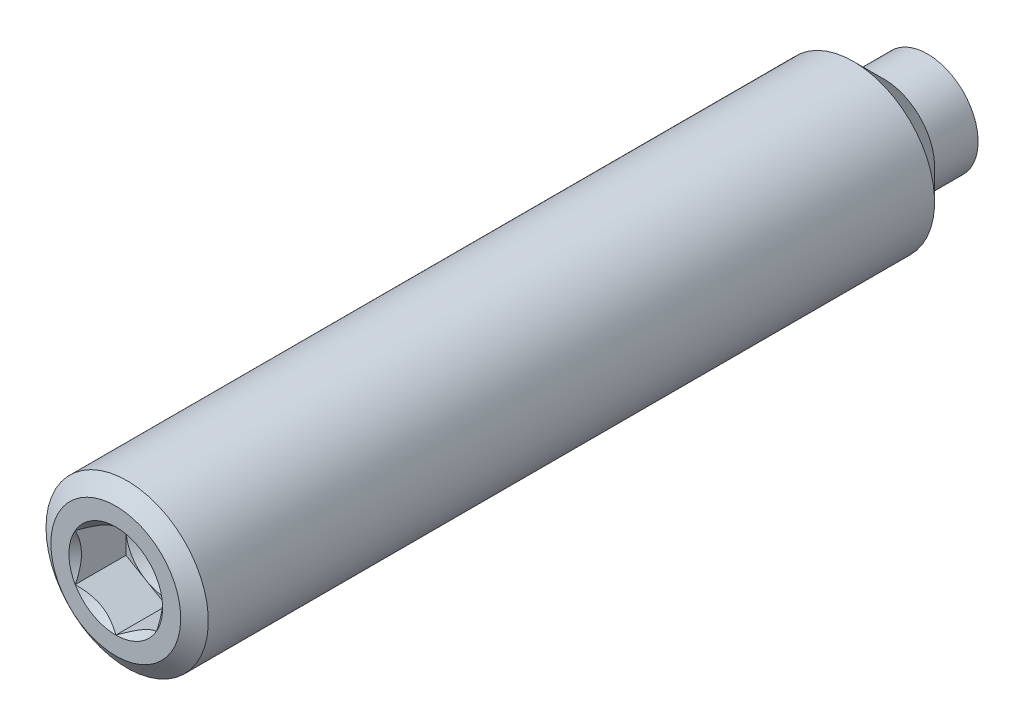
SolidWorks part; units mm, degrees
ref_plane "Front" through (0, 0, 0) normal (0, 0, 1) x (1, 0, 0)
ref_plane "Top" through (0, 0, 0) normal (0, 1, 0) x (1, 0, 0)
ref_plane "Right" through (0, 0, 0) normal (1, 0, 0) x (0, 0, -1)
sketch "Sketch22" plane through (0, 0, 0) normal (1, 0, 0) x (0, 0, -1)
  line L0 (-15.875, 0) -> (-15.875, 2.54)
  line L1 (-15.875, 2.54) -> (-15.4304, 3.175)
  line L2 (-15.4304, 3.175) -> (12.9794, 3.175)
  line L3 (12.9794, 3.175) -> (14.1732, 1.9812)
  line L4 (-15.875, 2.54) -> (-15.875, -2.54) construction
  line L5 (15.875, 0) -> (-15.875, 0)
  line L6 (0, 3.175) -> (0, -3.175) construction
  line L8 (14.1732, 1.9812) -> (15.875, 1.9812)
  line L9 (-14.2049, -3.175) -> (14.2049, -3.175) construction
  line L10 (15.875, 1.9812) -> (15.875, 0)
  line L11 (15.875, 1.9812) -> (15.875, -1.9812) construction
  dimension "D1" = 45
  dimension "Dia" = 6.35
  dimension "D2" = 5.08
  dimension "Length" = 31.75
  dimension "D3" = 35
  dimension "A" = 3.9624
  dimension "B" = 1.7018
revolve "Revolve1" add sketch "Sketch22" angle 360 about L5
ref_plane "Plane1" through (0, 0, -14.1732) normal (0, 0, 1) x (1, 0, 0)
sketch "Sketch27" plane through (0, 0, -14.1732) normal (0, 0, 1) x (1, 0, 0)
  circle A0 centre (0, 0) radius 3.175 construction
  circle A1 centre (0, 0) radius 3.175
curve "Helix/Spiral1" pitch 1.27 height 33.02 turns 26
sketch "Sketch28" plane through (0, 0, 0) normal (1, 0, 0) x (0, 0, -1)
  line L0 (14.1732, 3.175) -> (15.2845, 3.175)
  line L1 (15.2845, 3.175) -> (14.8082, 2.3501)
  line L2 (14.8082, 2.3501) -> (14.6495, 2.3501)
  line L3 (14.6495, 2.3501) -> (14.1732, 3.175)
  line L4 (14.4113, 2.7626) -> (15.0463, 2.7626) construction
  line L6 (-15.4304, 3.175) -> (12.9794, 3.175) construction
  line L7 (14.1732, 3.4925) -> (14.1732, -3.4925) construction
  dimension "D1" = 0.1588
  dimension "D2" = 0.635
  dimension "D3" = 60
sweep "Cut-Sweep2" [suppressed] cut profiles "Sketch28" path "Helix/Spiral1"
sketch "Sketch23" plane through (0, 0, 15.875) normal (0, 0, 1) x (1, 0, 0)
  line L1 (0, 1.8331) -> (-1.5875, 0.9165)
  line L2 (-1.5875, 0.9165) -> (-1.5875, -0.9165)
  line L3 (-1.5875, -0.9165) -> (0, -1.8331)
  line L4 (0, -1.8331) -> (1.5875, -0.9165)
  line L5 (1.5875, -0.9165) -> (1.5875, 0.9165)
  line L6 (1.5875, 0.9165) -> (0, 1.8331)
  circle A0 centre (0, 0) radius 1.5875 construction
  dimension "Hex" = 3.175
extrude "Cut-Extrude10" cut sketch "Sketch23" against normal blind 1.9844
sketch "Sketch24" plane through (0, 0, 15.875) normal (0, 0, 1) x (1, 0, 0)
  circle A0 centre (0, 0) radius 1.8331
extrude "Cut-Extrude11" cut sketch "Sketch24" against normal through all draft 45
sketch "Sketch26" plane through (0, 0, 13.8906) normal (0, 0, 1) x (1, 0, 0)
  circle A0 centre (0, 0) radius 1.5875 construction
  circle A1 centre (0, 0) radius 1.5875
extrude "Cut-Extrude12" cut sketch "Sketch26" against normal through all draft 60
sketch "Sketch30" plane through (0, 0, 0) normal (1, 0, 0) x (0, 0, -1)
  line L0 (-15.4304, 3.175) -> (12.9794, 3.175) construction
  line L1 (-15.875, 0) -> (-15.875, 2.54) construction
  line L2 (14.1732, 3.175) -> (14.1732, -3.175) construction
  line L3 (-14.2049, -3.175) -> (14.2049, -3.175) construction
  point P0 (-15.875, 3.175)
  point P1 (15.875, 3.175)
  point P2 (15.875, -3.175)
  point P11 (9.7282, -3.175)
  dimension "D1" = 4.445
equation "\"D1@Sketch28\" = \"D4@Helix/Spiral1\" * .125"
equation "\"D3@Helix/Spiral1\" = \"Length@Sketch22\" + \"D4@Helix/Spiral1\""
equation "\"D1@Sketch30\" = \"D4@Helix/Spiral1\" * 3.5"
equation "\"hex Depth@Cut-Extrude10\" = \"Hex@Sketch23\" * .625"
equation "\"D2@Sketch28\" = \"D4@Helix/Spiral1\" * .5"
equation "\"D2@Sketch22\" = \"Dia@Sketch22\" * .8"
